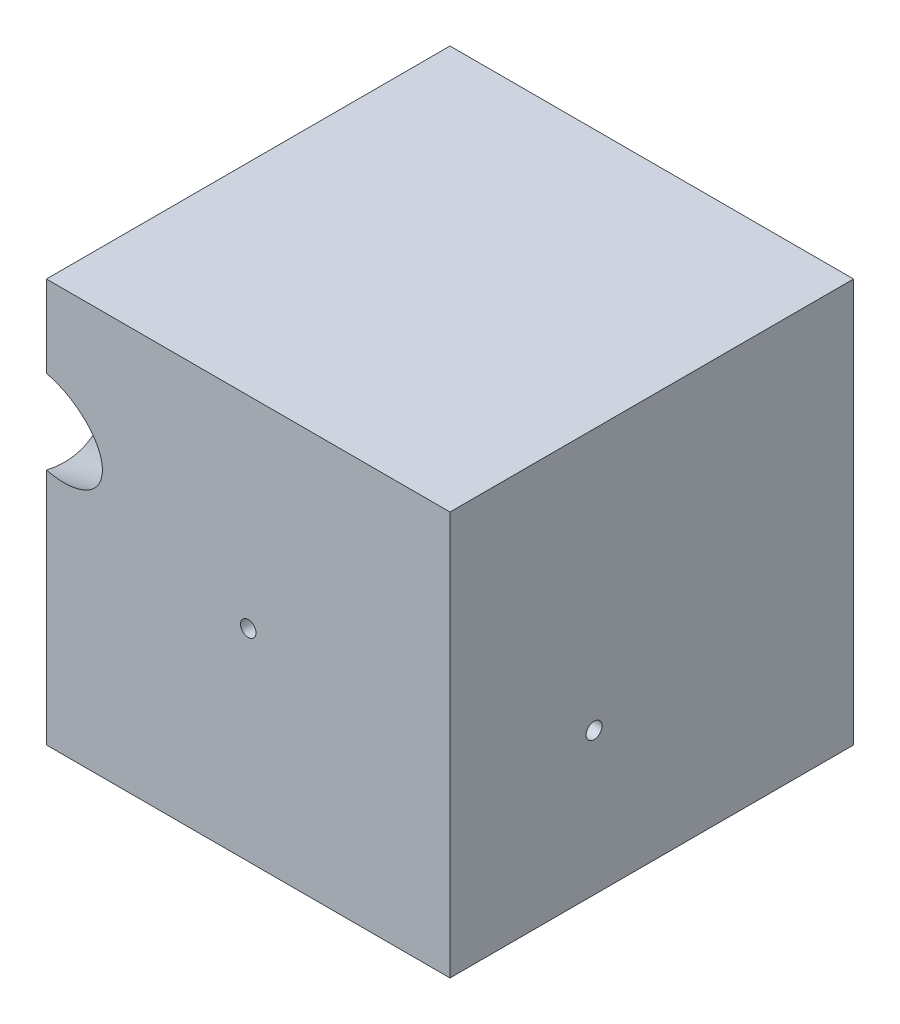
SolidWorks part; units mm, degrees
other "Markup1"
sketch "Sketch17" plane through (26, 26, 0) normal (0.2144, 0.2359, -0.9478) x (-0.9746, -0.0125, -0.2235)
other "Markup2"
sketch "Sketch18" plane through (26, 26, 52) normal (0.7408, 0.3225, 0.5893) x (0.4554, 0.4038, -0.7934)
material "ABS"
ref_plane "Front Plane" through (0, 0, 0) normal (0, 0, 1) x (1, 0, 0)
ref_plane "Top Plane" through (0, 0, 0) normal (0, 1, 0) x (1, 0, 0)
ref_plane "Right Plane" through (0, 0, 0) normal (1, 0, 0) x (0, 0, -1)
sketch "Square" plane through (0, 0, 0) normal (0, 0, 1) x (1, 0, 0)
  line L1 (-26, -26) -> (26, -26)
  line L2 (-26, -26) -> (-26, 26)
  line L3 (-26, 26) -> (26, 26)
  line L4 (26, -26) -> (26, 26)
  line L5 (-26, -26) -> (26, 26) construction
  line L6 (-26, 26) -> (26, -26) construction
  point P0 (0, 0)
  dimension "D1" = 52
extrude "Cube-Extrusion" add sketch "Square" along normal blind 52
ref_plane "StickPlane" through (-28.8889, 14.4444, 28.8889) normal (0.6667, -0.3333, -0.6667) x (-0.7454, -0.2981, -0.5963)
sketch "Stick-Hole" plane through (-28.8889, 14.4444, 28.8889) normal (0.6667, -0.3333, -0.6667) x (-0.7454, -0.2981, -0.5963)
  line L0 (-19.3793, 0) -> (-3.8759, -46.5102) construction
  circle A0 centre (-14.6358, -14.2302) radius 5.1
  dimension "D2" = 10.2
  dimension "D1" = 15
extrude "Stick-Cut" cut sketch "Stick-Hole" against normal through all from offset 15
sketch "Sketch12" plane through (0, 0, 52) normal (0, 0, 1) x (1, 0, 0)
  circle A0 centre (0, 0) radius 1
  dimension "D1" = 2
extrude "Cut-Extrude8" cut sketch "Sketch12" against normal blind 12
sketch "Sketch13" plane through (0, 0, 0) normal (0, 0, -1) x (-1, 0, 0)
  circle A0 centre (0, 0) radius 1
  dimension "D1" = 2
extrude "Cut-Extrude9" cut sketch "Sketch13" against normal blind 12
sketch "Sketch14" plane through (-26, 0, 0) normal (-1, 0, 0) x (0, 0, 1)
  line L0 (0, 26) -> (0, -26) construction
  line L1 (52, 26) -> (0, 26) construction
  line L2 (52, -26) -> (0, -26) construction
  circle A0 centre (10.5144, 15.4825) radius 1
  circle A1 centre (20.4493, -13.8146) radius 1
  dimension "D1" = 2
  dimension "D2" = 10.5144
  dimension "D3" = 10.5175
  dimension "D4" = 20.4493
  dimension "D5" = 12.1854
extrude "Cut-Extrude10" cut sketch "Sketch14" against normal blind 12
sketch "Sketch15" plane through (26, 0, 0) normal (1, 0, 0) x (0, 0, -1)
  circle A0 centre (-33.4399, -7.6506) radius 1.0307
extrude "Cut-Extrude11" cut sketch "Sketch15" against normal blind 12
sketch "Sketch16" plane through (0, -26, 0) normal (0, -1, 0) x (1, 0, 0)
  line L0 (-26, 52) -> (-26, 0) construction
  line L1 (-26, 0) -> (26, 0) construction
  circle A0 centre (-9, 44.28) radius 1
  dimension "D3" = 2
  dimension "D1" = 17
  dimension "D2" = 44.28
extrude "Cut-Extrude12" cut sketch "Sketch16" against normal blind 12
ref_plane "Plane1" through (0, 0, 0) normal (0.2823, 0.9593, 0) x (0.9593, -0.2823, 0)
